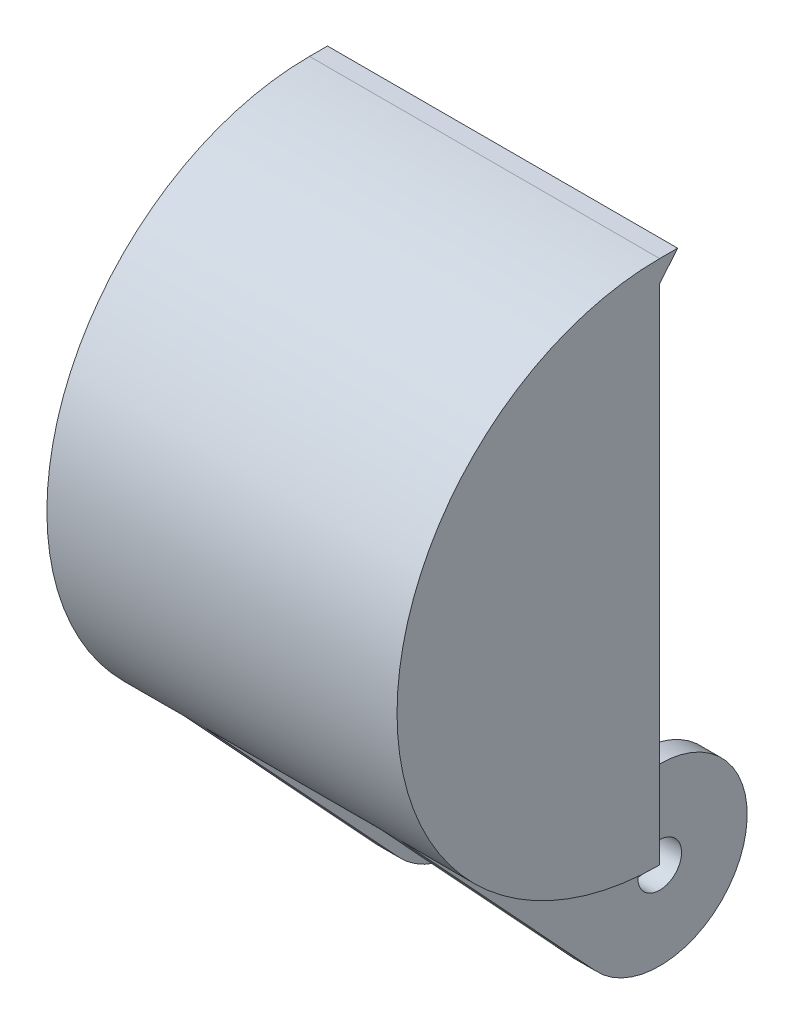
SolidWorks part; units mm, degrees
material "6061-T6 (SS)"
ref_plane "Front Plane" through (0, 0, 0) normal (0, 0, 1) x (1, 0, 0)
ref_plane "Top Plane" through (0, 0, 0) normal (0, 1, 0) x (1, 0, 0)
ref_plane "Right Plane" through (0, 0, 0) normal (1, 0, 0) x (0, 0, -1)
sketch "ExcavatorReferenceSize" plane through (0, 0, 0) normal (0, 1, 0) x (1, 0, 0)
  line L1 (-25.4, -12.7) -> (25.4, -12.7)
  line L2 (-25.4, -12.7) -> (-25.4, 12.7)
  line L3 (-25.4, 12.7) -> (25.4, 12.7)
  line L4 (25.4, -12.7) -> (25.4, 12.7)
  line L5 (-25.4, -12.7) -> (25.4, 12.7) construction
  line L6 (-25.4, 12.7) -> (25.4, -12.7) construction
  point P0 (0, 0)
  dimension "D1" = 25.4
  dimension "D2" = 50.8
sketch "Sketch2" plane through (0, 0, 0) normal (1, 0, 0) x (0, 0, -1)
  line L0 (0, 0) -> (0, 76.2)
  line L1 (0, 0) -> (8.9803, -8.9803) construction
  line L2 (0, 0) -> (0, 97.7406) construction
  arc A0 (0, 76.2) -> (0, 0) centre (0, 38.1) ccw
  dimension "D1" = 76.2
  dimension "D2" = 12.7
  dimension "D3" = 135
extrude "Boss-Extrude1" add sketch "Sketch2" along normal mid plane 50.8
shell "Shell1" thickness 3.175 removed face at (0, 38.1, 0)
chamfer "Chamfer1" [suppressed] distance 10 angle 45
sketch "Sketch4" plane through (0, 0, 0) normal (1, 0, 0) x (0, 0, -1)
  line L0 (0, 0) -> (31.6155, -31.6155) construction
  line L1 (0, 0) -> (0, 113.2937) construction
  circle A1 centre (9.525, -9.525) radius 12.7
  arc A2 (0, 73.025) -> (0, 3.175) centre (0, 38.1) ccw
  arc A3 (0, 73.025) -> (0, 3.175) centre (0, 38.1) ccw construction
  dimension "D1" = 25.4
  dimension "D2" = 135
  dimension "D3" = 12.7
extrude "Boss-Extrude3" add sketch "Sketch4" along normal mid plane 31.75
sketch "Sketch5" plane through (0, 0, 0) normal (1, 0, 0) x (0, 0, -1)
  line L1 (0, 3.175) -> (0, 0)
  line L3 (0, 0) -> (0, 76.2) construction
  line L4 (0, 3.175) -> (9.525, 3.175)
  line L5 (0, 0) -> (1.1247, 0)
  circle A0 centre (9.525, -9.525) radius 12.7 construction
  arc A1 (9.525, 3.175) -> (1.1247, 0) centre (9.525, -9.525) ccw
  dimension "D1" = 3.175
extrude "Boss-Extrude4" add sketch "Sketch5" along normal mid plane 31.75
sketch "Sketch6" plane through (0, 0, 0) normal (1, 0, 0) x (0, 0, -1)
  line L0 (0, 0) -> (8.9803, -8.9803) construction
  line L1 (0, 0) -> (0, 78.8833) construction
  circle A1 centre (8.9803, -8.9803) radius 12.7
  dimension "D3" = 25.4
  dimension "D1" = 225
extrude "Cut-Extrude2" cut sketch "Sketch6" against normal blind 12.7
extrude "Cut-Extrude3" cut sketch "Sketch6<2>" along normal blind 12.7
sketch "Sketch6<2>" plane through (0, 0, 0) normal (1, 0, 0) x (0, 0, -1) same geometry as "Sketch6"
sketch "Sketch7" plane through (-15.875, 0, 0) normal (-1, 0, 0) x (0, 0, 1)
  arc A1 (-9.525, 3.175) -> (-1.1247, 0) centre (-9.525, -9.525) ccw construction
  arc A2 (-9.525, 3.175) -> (-1.1247, 0) centre (-9.525, -9.525) ccw construction
  circle A3 centre (-9.525, -9.525) radius 3.175
  dimension "D1" = 6.35
extrude "Cut-Extrude4" cut sketch "Sketch7" against normal up to surface (31.75 mm away) up to face at (15.875, -4.1606, -4.835)
sketch "Sketch8" plane through (15.875, 0, 0) normal (1, 0, 0) x (0, 0, -1)
  line L3 (-27.9361, 12.1928) -> (0.213, -18.1607)
  line L6 (0.213, -18.1607) -> (5.0349, -21.4048)
  line L7 (-27.9361, 12.1928) -> (-25.2112, 13.9308)
  line L8 (5.0349, -21.4048) -> (1.1247, 0)
  line L9 (1.1247, 0) -> (0, 3.175)
  circle A3 centre (9.525, -9.525) radius 12.7 construction
  arc A5 (0, 76.2) -> (0, 0) centre (0, 38.1) ccw construction
  arc A6 (-27.9361, 12.1928) -> (0, 0) centre (0, 38.1) ccw construction
  arc A7 (22.225, -9.525) -> (0.213, -18.1607) centre (9.525, -9.525) ccw construction
  arc A9 (0, 73.025) -> (0, 3.175) centre (0, 38.1) ccw
  arc A10 (-25.2112, 13.9308) -> (0, 3.175) centre (0, 38.1) ccw
  arc A11 (1.1247, 0) -> (9.525, 3.175) centre (9.525, -9.525) ccw construction
  point P11 (-27.9361, 12.1928)
  point P12 (0.213, -18.1607)
  point P18 (-25.2112, 13.9308)
extrude "Boss-Extrude5" add sketch "Sketch8" against normal up to surface (31.75 mm away) up to face at (-15.875, -9.525, -6.35)
ref_plane "Plane1" through (0, -18.1607, 0) normal (0, 1, 0) x (1, 0, 0)
sketch "Sketch9" plane through (0, 0, 0) normal (1, 0, 0) x (0, 0, -1)
  line L5 (0, 3.175) -> (0, 0)
  line L13 (0, 3.175) -> (0, 0)
  line L15 (-27.9361, 12.1928) -> (0.213, -18.1607)
  line L16 (-27.9361, 12.1928) -> (0.213, -18.1607)
  line L21 (9.525, 3.175) -> (0, 3.175)
  line L22 (9.525, 3.175) -> (0, 3.175)
  arc A2 (-27.9361, 12.1928) -> (0, 0) centre (0, 38.1) ccw
  arc A3 (0.213, -18.1607) -> (9.525, 3.175) centre (9.525, -9.525) ccw
  arc A9 (-27.9361, 12.1928) -> (0, 0) centre (0, 38.1) ccw
  arc A10 (0.213, -18.1607) -> (9.525, 3.175) centre (9.525, -9.525) ccw
  dimension "D1" = 0
extrude "Cut-Extrude5" cut sketch "Sketch9" against normal mid plane 25.4
sketch "Sketch11" plane through (0, 0, 0) normal (1, 0, 0) x (0, 0, -1)
  line L0 (0, 76.2) -> (0, 73.025)
  line L8 (9.525, -9.525) -> (1.3049, 74.6125) construction
  line L9 (0, 76.2) -> (2.6098, 76.2)
  line L10 (2.6098, 76.2) -> (0, 73.025)
  circle A2 centre (9.525, -9.525) radius 3.175 construction
  arc A4 (0, 76.2) -> (0, 0) centre (0, 38.1) ccw construction
  arc A5 (0, 76.2) -> (0, 0) centre (0, 38.1) ccw construction
  circle A6 centre (9.525, -9.525) radius 3.175 construction
  point P3 (0.5785, 82.118)
  point P6 (0.9529, 74.6125)
  dimension "D1" = 45
extrude "Boss-Extrude6" add sketch "Sketch11" along normal mid plane 50.8 contours L10 L0 L9
ref_plane "Plane2" through (0, 73.025, 0) normal (0, -1, 0) x (-1, 0, 0)
fillet "Fillet2" radius 12.7 2 edges at (22.225, 38.1, 34.925) (-22.225, 38.1, 34.925)
